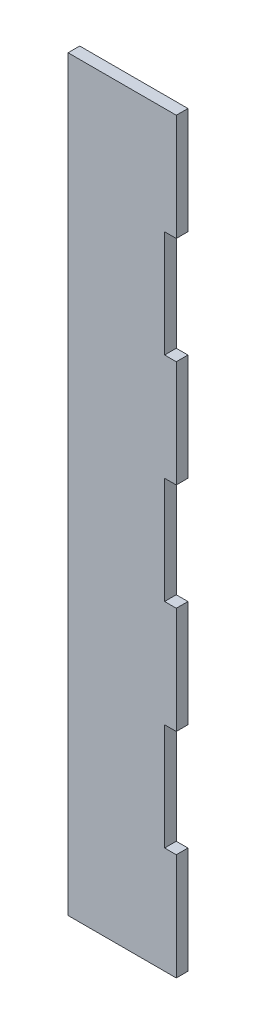
SolidWorks part; units mm, degrees
ref_plane "Front Plane" through (0, 0, 0) normal (0, 0, 1) x (1, 0, 0)
ref_plane "Top Plane" through (0, 0, 0) normal (0, 1, 0) x (1, 0, 0)
ref_plane "Right Plane" through (0, 0, 0) normal (1, 0, 0) x (0, 0, -1)
sketch "Sketch1" plane through (0, 0, 0) normal (0, 0, 1) x (1, 0, 0)
  line L0 (0, 101.6) -> (0, -101.6) construction
  line L1 (-6.35, 101.6) -> (6.35, 101.6)
  line L2 (-6.35, 101.6) -> (-6.35, -101.6)
  line L3 (-6.35, -101.6) -> (6.35, -101.6)
  line L4 (6.35, 101.6) -> (6.35, -101.6)
  line L5 (6.35, 72.5714) -> (6.35, 43.5429)
  line L6 (6.35, 101.6) -> (9.525, 101.6)
  line L7 (6.35, 101.6) -> (6.35, 72.5714)
  line L8 (6.35, 72.5714) -> (9.525, 72.5714)
  line L9 (9.525, 101.6) -> (9.525, 72.5714)
  line L10 (6.35, 72.5714) -> (9.525, 72.5714)
  line L11 (9.525, 72.5714) -> (9.525, 43.5429)
  line L12 (6.35, 43.5429) -> (9.525, 43.5429)
  line L13 (6.35, 43.5429) -> (6.35, 14.5143)
  line L14 (6.35, 43.5429) -> (9.525, 43.5429)
  line L15 (9.525, 43.5429) -> (9.525, 14.5143)
  line L16 (6.35, 14.5143) -> (9.525, 14.5143)
  line L17 (6.35, 14.5143) -> (6.35, -14.5143)
  line L18 (6.35, 14.5143) -> (9.525, 14.5143)
  line L19 (9.525, 14.5143) -> (9.525, -14.5143)
  line L20 (6.35, -14.5143) -> (9.525, -14.5143)
  line L21 (6.35, -14.5143) -> (6.35, -43.5429)
  line L22 (6.35, -14.5143) -> (9.525, -14.5143)
  line L23 (9.525, -14.5143) -> (9.525, -43.5429)
  line L24 (6.35, -43.5429) -> (9.525, -43.5429)
  line L25 (6.35, -43.5429) -> (6.35, -72.5714)
  line L26 (6.35, -43.5429) -> (9.525, -43.5429)
  line L27 (9.525, -43.5429) -> (9.525, -72.5714)
  line L28 (6.35, -72.5714) -> (9.525, -72.5714)
  line L29 (6.35, -72.5714) -> (6.35, -101.6)
  line L30 (6.35, -72.5714) -> (9.525, -72.5714)
  line L31 (9.525, -72.5714) -> (9.525, -101.6)
  line L32 (6.35, -101.6) -> (9.525, -101.6)
  point P6 (0, 0)
  dimension "D2" = 12.7
  dimension "D1" = 203.2
  dimension "D3" = 29.0286
  dimension "D4" = 3.175
  dimension "D5" = 7
extrude "Boss-Extrude1" add sketch "Sketch1" along normal blind 3.175 contours L0 L1 L2 L3 | L1 L0 L3 L4 | L9 L6 L4 L8 | L4 L16 L15 L12 | L4 L24 L23 L20 | L4 L32 L31 L28 region at (3.175, 0, 0) region at (-3.175, 0, 0) region at (7.9375, 87.0857, 0) region at (7.9375, -87.0857, 0) region at (7.9375, 29.0286, 0) region at (7.9375, -29.0286, 0)
sketch "Sketch2" plane through (-6.35, 0, 0) normal (-1, 0, 0) x (0, 0, 1)
  line L1 (0, 101.6) -> (3.175, 101.6)
  line L2 (0, 101.6) -> (0, -101.6)
  line L3 (0, -101.6) -> (3.175, -101.6)
  line L4 (3.175, 101.6) -> (3.175, -101.6)
extrude "Boss-Extrude2" add sketch "Sketch2" along normal blind 13.56
equation "\"Height\"= 12in"
equation "\"Depth\"= 7in"
equation "\"WallThickness\"= 0.125in"
equation "\"FloorThickness\"= 0.25in"
equation "\"Width\" = 30in"
equation "\"D1@Boss-Extrude1\"=\"WallThickness\""
equation "\"D3@Sketch1\"=\"D1@Sketch1\"/\"D5@Sketch1\""
equation "\"D4@Sketch1\"=\"WallThickness\""
